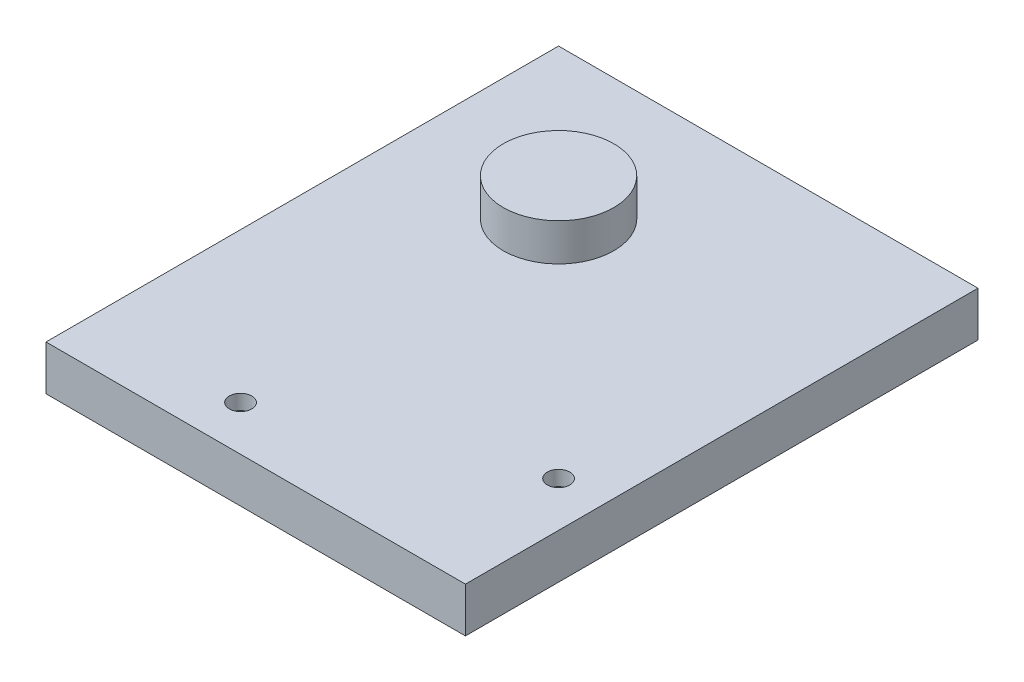
SolidWorks part; units mm, degrees
ref_plane "Front Plane" through (0, 0, 0) normal (0, 0, 1) x (1, 0, 0)
ref_plane "Top Plane" through (0, 0, 0) normal (0, 1, 0) x (1, 0, 0)
ref_plane "Right Plane" through (0, 0, 0) normal (1, 0, 0) x (0, 0, -1)
sketch "Sketch1" plane through (0, 0, 0) normal (0, 1, 0) x (1, 0, 0)
  line L0 (0, 0) -> (30.052, -30.052) construction
  line L1 (0, -42.5) -> (0, 0) construction
  line L3 (-20, 20) -> (36.052, 20)
  line L4 (-20, 20) -> (-20, -48.5)
  line L5 (-20, -48.5) -> (36.052, -48.5)
  line L6 (36.052, 20) -> (36.052, -48.5)
  circle A0 centre (0, 0) radius 7.39
  circle A1 centre (0, -42.5) radius 1.5
  circle A2 centre (30.052, -30.052) radius 1.5
  dimension "D3" = 3
  dimension "D4" = 3
  dimension "D5" = 14.78
  dimension "D1" = 42.5
  dimension "D2" = 42.5
  dimension "D6" = 45
  dimension "D7" = 6
  dimension "D8" = 6
  dimension "D9" = 20
  dimension "D10" = 20
extrude "Boss-Extrude1" add sketch "Sketch1" against normal blind 6 contours A0 | L6 L3 L4 L5 A2 A1 A0 region at (8.3758, 0, 14.8339) region at (0, 0, 0)
extrude "Boss-Extrude2" add sketch "Sketch1<3>" along normal blind 5 contours A0 region at (0, 0, 0)
sketch "Sketch1<3>" plane through (0, 0, 0) normal (0, 1, 0) x (1, 0, 0) same geometry as "Sketch1"
sketch "Sketch2" plane through (0, -6, 0) normal (0, -1, 0) x (1, 0, 0)
  circle A0 centre (0, 42.5) radius 1.95
  circle A1 centre (30.052, 30.052) radius 1.95
  circle M1 centre (30.052, 30.052) radius 1.5
  circle M2 centre (0, 42.5) radius 1.5
  dimension "D1" = 3.9
extrude "Cut-Extrude1" cut sketch "Sketch2" against normal blind 4 contours A0 M2 | A1 M1 region at (-1.8948, -6, 42.5) region at (28.1572, -6, 30.052)
